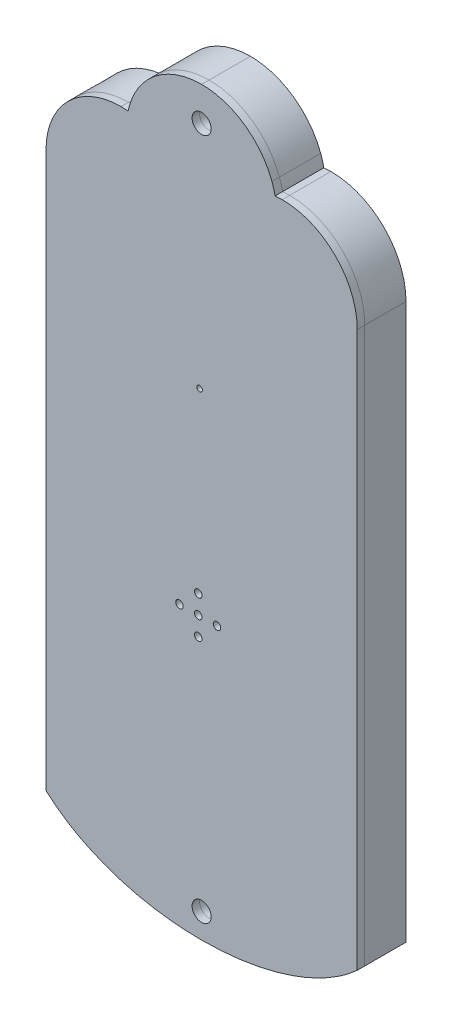
SolidWorks part; units mm, degrees
note: The reader was unsure of these and kept them because the rebuilt part matched: shared geometry of "草图3<3>", "草图3<4>", "草图3<5>", "草图3<6>", "草图3<7>", "草图5<4>", "草图5<5>", "草图5<6>".
ref_plane "前视基准面" through (0, 0, 0) normal (0, 0, 1) x (1, 0, 0)
ref_plane "上视基准面" through (0, 0, 0) normal (0, 1, 0) x (1, 0, 0)
ref_plane "右视基准面" through (0, 0, 0) normal (1, 0, 0) x (0, 0, -1)
other "Configuration Table"
sketch "草图1" plane through (0, 0, 0) normal (0, 0, 1) x (1, 0, 0)
  line L4 (-41.5008, 68.1408) -> (-41.5008, -79.8592)
  line L5 (41.5008, 68.1408) -> (41.5008, -79.8592)
  circle A0 centre (0, 95) radius 2.55
  circle A1 centre (0, -87) radius 2.55
  spline S0 degree 3 poles (41.5008, 68.1408) (41.5008, 79.1863) (32.5473, 88.1398) (21.5018, 88.1398) knots 0 0 0 0 1 1 1 1
  spline S1 degree 3 poles (21.5018, 88.1398) (20.8598, 88.1398) (20.2212, 88.108) (19.5933, 88.048) knots 1 1 1 1 2 2 2 2
  spline S2 degree 3 poles (19.5933, 88.048) (19.3887, 89.0464) (19.1064, 90.0201) (18.7607, 90.962) knots 2 2 2 2 3 3 3 3
  spline S3 degree 3 poles (18.7607, 90.962) (15.9385, 98.582) (8.6043, 104.0148) (0, 104.0148) knots 3 3 3 3 4 4 4 4
  spline S4 degree 3 poles (0, 104.0148) (-8.6043, 104.0148) (-15.9385, 98.582) (-18.7607, 90.962) knots 4 4 4 4 5 5 5 5
  spline S5 degree 3 poles (-18.7607, 90.962) (-19.1065, 90.0201) (-19.3887, 89.0464) (-19.5933, 88.048) knots 5 5 5 5 6 6 6 6
  spline S6 degree 3 poles (-19.5933, 88.048) (-20.2212, 88.108) (-20.8562, 88.1398) (-21.4983, 88.1398) knots 6 6 6 6 7 7 7 7
  spline S7 degree 3 poles (-21.4983, 88.1398) (-32.5473, 88.1398) (-41.5008, 79.1863) (-41.5008, 68.1408) knots 7 7 7 7 8 8 8 8
  spline S9 degree 3 poles (-41.5008, -79.8592) (-38.3893, -82.7026) (-34.5687, -85.2073) (-30.1978, -87.2781) knots 11 11 11 11 12 12 12 12
  spline S10 degree 3 poles (-30.1978, -87.2781) (-21.7805, -91.2681) (-11.3242, -93.6281) (0, -93.6281) knots 12 12 12 12 13 13 13 13
  spline S11 degree 3 poles (0, -93.6281) (11.3242, -93.6281) (21.7805, -91.2681) (30.1978, -87.2781) knots 13 13 13 13 14 14 14 14
  spline S12 degree 3 poles (30.1978, -87.2781) (34.5687, -85.2073) (38.3893, -82.7026) (41.5008, -79.8592) knots 14 14 14 14 15 15 15 15
extrude "凸台-拉伸1" add sketch "草图1" along normal blind 11
ref_plane "基准面1" through (0, 0, 11) normal (0, 0, 1) x (1, 0, 0)
sketch "草图2" plane through (0, 0, 11) normal (0, 0, 1) x (1, 0, 0)
  line L4 (-39, 72.5618) -> (-31.8531, 72.5618)
  line L5 (39, 72.5618) -> (39, -79.4382)
  line L6 (39, -79.4382) -> (33.5901, -79.4382)
  line L7 (-39, -79.4382) -> (-39, 72.5618)
  line L8 (31.8531, 72.5618) -> (39, 72.5618)
  line L9 (-6.9191, -84.6699) -> (-6.9191, -88.937)
  line L10 (-6.9191, -88.937) -> (-32.7537, -79.6163)
  line L11 (5.9471, -84.6699) -> (5.9471, -89.5326)
  line L12 (5.9471, -89.5326) -> (32.543, -79.6269)
  line L13 (-33.7719, -79.4382) -> (-39, -79.4382)
  line L15 (-3.9191, -81.6699) -> (2.9471, -81.6699)
  arc A0 (-32.7537, -79.6163) -> (-33.7719, -79.4382) centre (-33.7719, -82.4382) ccw
  arc A1 (32.543, -79.6269) -> (33.5901, -79.4382) centre (33.5901, -82.4382) cw
  arc A2 (2.9471, -81.6699) -> (5.9471, -84.6699) centre (2.9471, -84.6699) cw
  arc A3 (-3.9191, -81.6699) -> (-6.9191, -84.6699) centre (-3.9191, -84.6699) ccw
  ellipse E0 centre (0, 72.5618) end of major axis (31.8531, 72.5618) minor radius 16.2594 (31.8531, 72.5618) -> (-31.8531, 72.5618) ccw
  point P11 (0, 72.5618)
  point P20 (-33.2472, -79.4382)
  dimension "D1" = 3
extrude "切除-拉伸1" cut sketch "草图2" against normal blind 12
sketch "草图3" plane through (0, 0, 11) normal (0, 0, 1) x (1, 0, 0)
  line L1 (35.4265, -17.4382) -> (39, -17.4382)
  line L2 (39, -79.4382) -> (39, 72.5618) construction
  line L3 (39, -17.4382) -> (39, 72.5618)
  line L4 (39, 72.5618) -> (35.4265, 72.5618)
  line L6 (35.4265, -17.4382) -> (39, -17.4382)
  line L8 (35.4265, -79.4382) -> (39, -79.4382)
  line L9 (39, -17.4382) -> (39, -79.4382)
  line L10 (-39, 72.5618) -> (-35.4265, 72.5618)
  line L11 (-39, 72.5618) -> (-39, 37.5618)
  line L12 (-39, 37.5618) -> (-35.4265, 37.5618)
  line L14 (-39, 37.5618) -> (-35.4265, 37.5618)
  line L15 (-39, 37.5618) -> (-39, 17.5618)
  line L16 (-39, 17.5618) -> (-35.4265, 17.5618)
  line L18 (-39, 17.5618) -> (-35.4265, 17.5618)
  line L19 (-39, 17.5618) -> (-39, -17.4382)
  line L20 (-39, -17.4382) -> (-35.4265, -17.4382)
  line L22 (-39, -17.4382) -> (-35.4265, -17.4382)
  line L23 (-39, -17.4382) -> (-39, -79.4382)
  line L24 (-39, -79.4382) -> (-35.4265, -79.4382)
  line L26 (-39, 45.8739) -> (-35.4265, 45.8739)
  line L27 (20.5419, -14.1047) -> (32.8279, -14.1047)
  line L28 (35.4265, -36.1381) -> (39, -36.1381)
  line L29 (35.4265, -61.3133) -> (39, -61.3133)
  line L30 (-30.8782, -14.1047) -> (-22.35, -14.1047)
  line L32 (-30.7801, -21.1833) -> (-22.7965, -21.1833)
  line L34 (20.9884, -21.1833) -> (32.9261, -21.1833)
  line L35 (-39, 65.5697) -> (-35.4265, 65.5697)
  line L36 (-39, -8.0335) -> (-35.4265, -8.0335)
  line L37 (-39, -26.8837) -> (-35.4265, -26.8837)
  line L38 (-39, -45.9131) -> (-35.4265, -45.9131)
  line L39 (-39, -52.894) -> (-35.4265, -52.894)
  line L40 (-39, -72.037) -> (-35.4265, -72.037)
  line L41 (35.4265, 65.5697) -> (39, 65.5697)
  line L42 (35.4265, 34.3099) -> (39, 34.3099)
  line L43 (35.4265, 21.7239) -> (39, 21.7239)
  line L44 (35.4265, -8.0335) -> (39, -8.0335)
  line L45 (35.4265, 72.5618) -> (35.4265, -79.4382)
  line L46 (-35.4265, 72.5618) -> (-35.4265, -79.4382)
  line L47 (-30.8782, -14.1047) -> (-35.4265, -14.1047)
  line L48 (-30.7801, -21.1833) -> (-35.4265, -21.1833)
  line L49 (32.8279, -14.1047) -> (35.4265, -14.1047)
  line L50 (32.9261, -21.1833) -> (35.4265, -21.1833)
  circle A0 centre (-0.904, -19.0108) radius 20
  circle A1 centre (-0.904, -19.0108) radius 22
extrude "凸台-拉伸2" add sketch "草图3" against normal blind 9 separate body contours L4 L45 L41 L3 | L46 L10 L11 L35 | L46 L26 L11 L12 | L42 L45 L43 L3 | L44 L45 L1 L3 | L46 L36 L19 L20
extrude "凸台-拉伸3" add sketch "草图3<3>" against normal blind 2 separate body contours L46 L35 L11 L26 | L41 L45 L42 L3 | L43 L45 L44 L3 | L46 L16 L19 L36 | L46 L12 L15 L16
sketch "草图3<3>" plane through (0, 0, 11) normal (0, 0, 1) x (1, 0, 0) same geometry as "草图3"
extrude "凸台-拉伸4" add sketch "草图3<4>" against normal blind 2
sketch "草图3<4>" plane through (0, 0, 11) normal (0, 0, 1) x (1, 0, 0) same geometry as "草图3"
extrude "凸台-拉伸5" add sketch "草图3<5>" against normal blind 5 contours A1 A0
sketch "草图3<5>" plane through (0, 0, 11) normal (0, 0, 1) x (1, 0, 0) same geometry as "草图3"
extrude "凸台-拉伸6" add sketch "草图3<6>" against normal blind 8.5 separate body
sketch "草图3<6>" plane through (0, 0, 11) normal (0, 0, 1) x (1, 0, 0) same geometry as "草图3"
extrude "凸台-拉伸7" add sketch "草图3<7>" against normal blind 2 separate body contours L46 L37 L23 L38 | L46 L39 L23 L40 | L28 L45 L29 L9
sketch "草图3<7>" plane through (0, 0, 11) normal (0, 0, 1) x (1, 0, 0) same geometry as "草图3"
ref_plane "基准面2" through (0, 0, 11) normal (0, 0, 1) x (1, 0, 0)
sketch "草图5" plane through (0, 0, 11) normal (0, 0, 1) x (1, 0, 0)
  line L0 (26.5783, 72.5618) -> (26.5783, 46.5618) construction
  line L1 (26.5783, 46.5618) -> (35.4265, 46.5618)
  line L3 (35.4265, 46.5618) -> (35.4265, 48.7052)
  line L4 (-41.5008, 68.1408) -> (-41.5008, -79.8592)
  line L5 (41.5008, 68.1408) -> (41.5008, -79.8592)
  line L6 (35.4265, 48.7052) -> (26.5783, 48.7052)
  line L7 (26.5783, 48.7052) -> (26.5783, 46.5618)
  line L8 (26.5783, 46.5618) -> (26.5783, 44.1796)
  line L9 (26.5783, 44.1796) -> (35.4265, 44.1796)
  line L10 (35.4265, 44.1796) -> (35.4265, 46.5618)
  line L11 (-10.106, 14.7667) -> (-10.106, 6.0897)
  line L13 (-10.106, 14.7667) -> (-11.9222, 14.7667)
  line L14 (-11.9222, 14.7667) -> (-11.9222, 4.6475)
  line L15 (-11.9222, 4.6475) -> (-5.538, 4.6475)
  line L16 (-10.106, 6.0897) -> (-5.538, 6.0897)
  line L18 (-5.538, 6.0897) -> (-5.538, 4.6475)
  line L19 (-10.106, 9.0897) -> (-5.538, 9.0897)
  line L20 (-5.538, 9.0897) -> (-5.538, 6.0897)
  line L21 (-10.106, 36.8239) -> (-10.106, 41.8535)
  line L22 (-10.106, 41.8535) -> (-11.9222, 41.8535)
  line L23 (-11.9222, 41.8535) -> (-11.9222, 36.8239)
  line L24 (-11.9222, 36.8239) -> (-10.106, 36.8239)
  line L25 (-10.106, 41.8535) -> (-7.3703, 41.8535)
  line L26 (-7.3703, 41.8535) -> (-7.3703, 36.8239)
  line L27 (-7.3703, 36.8239) -> (-10.106, 36.8239)
  circle A0 centre (0, 95) radius 2.55
  circle A1 centre (0, -87) radius 2.55
  circle A2 centre (-0.5438, 33.4934) radius 0.75
  circle A3 centre (-0.904, -19.0108) radius 1
  circle A5 centre (-0.904, -14.0108) radius 1
  circle A6 centre (4.096, -19.0108) radius 1
  circle A7 centre (-0.904, -24.0108) radius 1
  circle A8 centre (-5.904, -19.0108) radius 1
  spline S0 degree 3 poles (41.5008, 68.1408) (41.5008, 79.1863) (32.5473, 88.1398) (21.5018, 88.1398) knots 0 0 0 0 1 1 1 1
  spline S1 degree 3 poles (21.5018, 88.1398) (20.8598, 88.1398) (20.2212, 88.108) (19.5933, 88.048) knots 1 1 1 1 2 2 2 2
  spline S2 degree 3 poles (19.5933, 88.048) (19.3887, 89.0464) (19.1064, 90.0201) (18.7607, 90.962) knots 2 2 2 2 3 3 3 3
  spline S3 degree 3 poles (18.7607, 90.962) (15.9385, 98.582) (8.6043, 104.0148) (0, 104.0148) knots 3 3 3 3 4 4 4 4
  spline S4 degree 3 poles (0, 104.0148) (-8.6043, 104.0148) (-15.9385, 98.582) (-18.7607, 90.962) knots 4 4 4 4 5 5 5 5
  spline S5 degree 3 poles (-18.7607, 90.962) (-19.1065, 90.0201) (-19.3887, 89.0464) (-19.5933, 88.048) knots 5 5 5 5 6 6 6 6
  spline S6 degree 3 poles (-19.5933, 88.048) (-20.2212, 88.108) (-20.8562, 88.1398) (-21.4983, 88.1398) knots 6 6 6 6 7 7 7 7
  spline S7 degree 3 poles (-21.4983, 88.1398) (-32.5473, 88.1398) (-41.5008, 79.1863) (-41.5008, 68.1408) knots 7 7 7 7 8 8 8 8
  spline S9 degree 3 poles (-41.5008, -79.8592) (-38.3893, -82.7026) (-34.5687, -85.2073) (-30.1978, -87.2781) knots 11 11 11 11 12 12 12 12
  spline S10 degree 3 poles (-30.1978, -87.2781) (-21.7805, -91.2681) (-11.3242, -93.6281) (0, -93.6281) knots 12 12 12 12 13 13 13 13
  spline S11 degree 3 poles (0, -93.6281) (11.3242, -93.6281) (21.7805, -91.2681) (30.1978, -87.2781) knots 13 13 13 13 14 14 14 14
  spline S12 degree 3 poles (30.1978, -87.2781) (34.5687, -85.2073) (38.3893, -82.7026) (41.5008, -79.8592) knots 14 14 14 14 15 15 15 15
  point P49 (-0.904, -19.0108)
  point P52 (-0.904, -19.0108)
extrude "凸台-拉伸8" add sketch "草图5" along normal blind 2 separate body
extrude "凸台-拉伸9" add sketch "草图5<4>" against normal blind 9 separate body contours L6 L7 L1 L3 | L18 L16 L11 L13 L14 L15 | L23 L24 L21 L22
sketch "草图5<4>" plane through (0, 0, 11) normal (0, 0, 1) x (1, 0, 0) same geometry as "草图5"
extrude "凸台-拉伸10" add sketch "草图5<5>" against normal blind 7 separate body contours L9 L10 L1 L8 | L20 L19 L11 L16
sketch "草图5<5>" plane through (0, 0, 11) normal (0, 0, 1) x (1, 0, 0) same geometry as "草图5"
extrude "凸台-拉伸11" add sketch "草图5<6>" against normal blind 6 separate body contours L27 L26 L25 L21
sketch "草图5<6>" plane through (0, 0, 11) normal (0, 0, 1) x (1, 0, 0) same geometry as "草图5"
equation "\"、\"=3"
